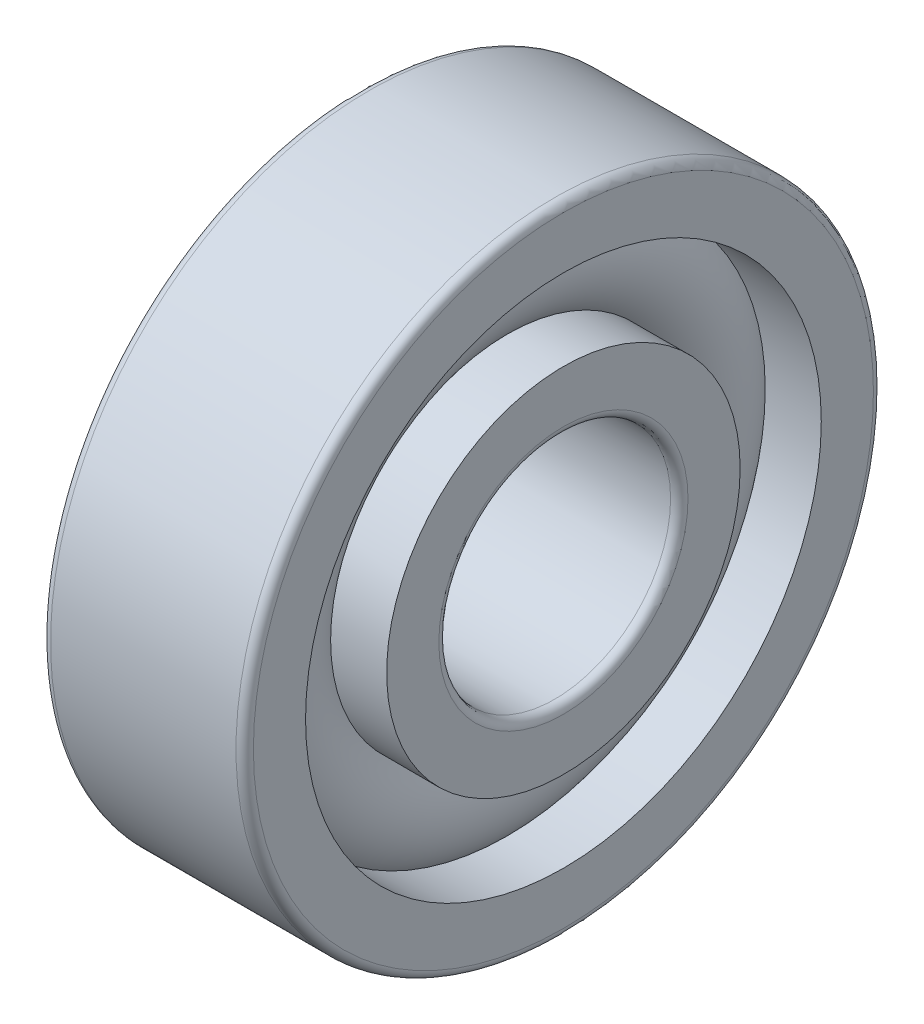
SolidWorks part; units mm, degrees
ref_plane "Plane1" through (0, 0, 0) normal (0, 0, 1) x (1, 0, 0)
ref_plane "Plane2" through (0, 0, 0) normal (0, 1, 0) x (1, 0, 0)
ref_plane "Plane3" through (0, 0, 0) normal (1, 0, 0) x (0, 0, -1)
other "Configuration Table"
sketch "Clipboard" plane through (0, 0, 0) normal (0, 0, 1) x (1, 0, 0)
  line L0 (-10, 0) -> (10, 0) construction
  line L1 (0, 0) -> (22.3471, -0.7804)
  line L2 (0, 0) -> (7.4954, 0.2617)
  line L3 (0, 0) -> (22.3471, -0.7804)
  line L4 (0, 0) -> (-22.3573, -0.3902)
  dimension "BallCLRad" = 7.5
sketch "CagSpiSke" plane through (0, 0, 0) normal (0, 0, 1) x (1, 0, 0)
  line L0 (0.21, 7.15) -> (0.21, 7.85)
  line L1 (0.21, 7.85) -> (-0.21, 7.85)
  line L2 (-0.21, 7.85) -> (-0.21, 7.15)
  line L3 (-0.21, 7.15) -> (0.21, 7.15)
  line L4 (-20.6375, 0) -> (20.6375, 0) construction
  line L5 (0, 0) -> (0, 23.7692) construction
  dimension "OD" = 15.7
  dimension "ID" = 14.3
revolve "CageSpine" add sketch "CagSpiSke" angle 0.001 about L4 reverse direction yes
ref_axis "Axis1" through (-50, 0, 0) along (1, 0, 0)
sketch "CagBalSke" plane through (0, 0, 0) normal (0, 0, 1) x (1, 0, 0)
  line L0 (-2.31, 7.5) -> (2.31, 7.5)
  line L1 (-1.905, 7.5) -> (1.905, 7.5) construction
  line L2 (-10, 0) -> (10, 0) construction
  line L3 (0, 0) -> (0, 24) construction
  arc A0 (2.31, 7.5) -> (-2.31, 7.5) centre (0, 7.5) cw
  dimension "BallCLRad" = 7.5
revolve "CageBall" [suppressed] add sketch "CagBalSke" angle 360 about L1 reverse direction yes
pattern_circular "CageBalls" [suppressed] count 2 every 180 about axis through (-50, 0, 0) along (1, 0, 0)
sketch "CagTrmODSke" plane through (0, 0, 0) normal (0, 0, 1) x (1, 0, 0)
  line L0 (2.311, 7.85) -> (2.311, 9.811)
  line L1 (2.311, 9.811) -> (-2.311, 9.811)
  line L2 (-2.311, 9.811) -> (-2.311, 7.85)
  line L3 (-2.311, 7.85) -> (2.311, 7.85)
  line L4 (-20.6375, 0) -> (20.6375, 0) construction
  line L5 (0, 0) -> (0, 25) construction
  dimension "Width" = 4.622
  dimension "ID" = 15.7
  dimension "OD" = 19.622
revolve "CageTrimOD" [suppressed] cut sketch "CagTrmODSke" angle 360 about L4 reverse direction yes
sketch "CagTrmIDSke" plane through (0, 0, 0) normal (0, 0, 1) x (1, 0, 0)
  line L0 (2.311, 5.191) -> (2.311, 7.15)
  line L1 (2.311, 7.15) -> (-2.311, 7.15)
  line L2 (-2.311, 7.15) -> (-2.311, 5.191)
  line L3 (-2.311, 5.191) -> (2.311, 5.191)
  line L4 (-20.6375, 0) -> (20.6375, 0) construction
  line L5 (0, 0) -> (0, 25) construction
  dimension "Width" = 4.622
  dimension "ID" = 10.382
  dimension "OD" = 14.3
revolve "CageTrimID" [suppressed] cut sketch "CagTrmIDSke" angle 360 about L4 reverse direction yes
sketch "BalSimSke" plane through (0, 0, 0) normal (0, 0, 1) x (1, 0, 0)
  line L0 (-10, 0) -> (10, 0) construction
  line L1 (-10, 7.5) -> (10, 7.5) construction
  line L2 (0, 0) -> (0, 23) construction
  circle A0 centre (0, 7.5) radius 2.1
  dimension "BallCLRad" = 7.5
  dimension "Ball_diameter" = 4.2
revolve "BallsSimplified" add sketch "BalSimSke" angle 360 about L0
sketch "BalDetSke" plane through (0, 0, 0) normal (0, 0, 1) x (1, 0, 0)
  line L0 (-2.1, 7.5) -> (2.1, 7.5)
  line L1 (-1.905, 7.5) -> (1.905, 7.5) construction
  line L2 (0, 0) -> (0, 25) construction
  arc A0 (2.1, 7.5) -> (-2.1, 7.5) centre (0, 7.5) cw
  dimension "BallCLRad" = 7.5
  dimension "Ball_diameter" = 4.2
revolve "BallDetailed" [suppressed] add sketch "BalDetSke" angle 360 about L1 reverse direction yes
sketch "InnRacSke" plane through (0, 0, 0) normal (0, 0, 1) x (1, 0, 0)
  line L0 (-1.5315, 6.1) -> (-3.5, 6.1)
  line L1 (-3.5, 6.1) -> (-3.5, 4.3)
  line L2 (-3.2, 4) -> (3.2, 4)
  line L3 (3.5, 4.3) -> (3.5, 6.1)
  line L4 (3.5, 6.1) -> (1.5315, 6.1)
  line L5 (-20.6375, 0) -> (20.6375, 0) construction
  line L6 (0, 0) -> (0, 30) construction
  arc A0 (-3.5, 4.3) -> (-3.2, 4) centre (-3.2, 4.3) ccw
  arc A1 (3.2, 4) -> (3.5, 4.3) centre (3.2, 4.3) ccw
  arc A2 (1.5315, 6.1) -> (-1.5315, 6.1) centre (0, 7.5) cw
  dimension "BallCLRad" = 7.5
  dimension "Fillet_radius" = 0.3
  dimension "Ball_diameter" = 4.15
  dimension "ID" = 8
  dimension "OD" = 12.2
  dimension "Width" = 7
revolve "InnerRace" add sketch "InnRacSke" angle 360 about L5 reverse direction yes
sketch "OutRacSke" plane through (0, 0, 0) normal (0, 0, 1) x (1, 0, 0)
  line L0 (-1.5315, 8.9) -> (-3.5, 8.9)
  line L1 (-3.5, 8.9) -> (-3.5, 10.7)
  line L2 (-3.2, 11) -> (3.2, 11)
  line L3 (3.5, 10.7) -> (3.5, 8.9)
  line L4 (3.5, 8.9) -> (1.5315, 8.9)
  line L5 (-20.6375, 0) -> (20.6375, 0) construction
  line L6 (0, 0) -> (0, 30) construction
  arc A0 (-3.5, 10.7) -> (-3.2, 11) centre (-3.2, 10.7) cw
  arc A1 (3.2, 11) -> (3.5, 10.7) centre (3.2, 10.7) cw
  arc A2 (1.5315, 8.9) -> (-1.5315, 8.9) centre (0, 7.5) ccw
  dimension "BallCLRad" = 7.5
  dimension "Fillet_radius" = 0.3
  dimension "Ball_diameter" = 4.15
  dimension "Width" = 7
revolve "OuterRace" add sketch "OutRacSke" angle 360 about L5 reverse direction yes
pattern_circular "BallsDetailed" [suppressed] count 2 every 180 about axis through (-50, 0, 0) along (1, 0, 0)
equation "\"BallCLRad@Clipboard\" = ( \"OD@OutRacSke\" + \"ID@InnRacSke\" ) / 4"
equation "\"BallCLRad@BalSimSke\" = \"BallCLRad@Clipboard\""
equation "\"BallCLRad@BalDetSke\" = \"BallCLRad@Clipboard\""
equation "\"BallCLRad@InnRacSke\" = \"BallCLRad@Clipboard\""
equation "\"BallCLRad@OutRacSke\" = \"BallCLRad@Clipboard\""
equation "\"Ball_diameter@InnRacSke\" = \"Ball_diameter@BalDetSke\" - 0.05"
equation "\"Ball_diameter@OutRacSke\" = \"Ball_diameter@BalDetSke\" - 0.05"
equation "\"Ball_diameter@BalSimSke\" = \"Ball_diameter@BalDetSke\""
equation "\"Width@OutRacSke\" = \"Width@InnRacSke\""
equation "\"Fillet_radius@OutRacSke\" = \"Fillet_radius@InnRacSke\""
equation "\"Max_count@Clipboard\" = int( 3.14159265 / atn(( \"Ball_diameter@BalDetSke\" / 2) / sqr( \"BallCLRad@Clipboard\"  *  \"BallCLRad@Clipboard\" - ( \"Ball_diameter@BalDetSke\" / 2) *  ( \"Ball_diameter@BalDetSke\" / 2))))"
equation "\"Max_count@Clipboard\" = ((sgn( \"Max_count@Clipboard\" - \"Count@Clipboard\" )-1)*( \"Max_count@Clipboard\" - \"Count@Clipboard\" ))/-2+ \"Count@Clipboard\""
equation "\"Count@BallsDetailed\" = int( \"Show_count@Clipboard\" ) "
equation "\"Count@BallsDetailed\" = ((sgn( \"Count@BallsDetailed\" - \"Max_count@Clipboard\" )-1)*( \"Count@BallsDetailed\" - \"Max_count@Clipboard\" ))/-2+ \"Max_count@Clipboard\""
equation "\"Count@BallsDetailed\" = ((sgn( \"Count@BallsDetailed\" - \"Min_count@Clipboard\" )+1)*( \"Count@BallsDetailed\" - \"Min_count@Clipboard\"))/2 +\"Min_count@Clipboard\""
equation "\"Angle@BallsDetailed\" = 360.0 / \"Max_count@Clipboard\""
equation "\"BallCLRad@CagBalSke\" = \"BallCLRad@Clipboard\""
equation "\"Count@CageBalls\" = \"Count@BallsDetailed\""
equation "\"Angle@CageBalls\" = \"Angle@BallsDetailed\""
equation "\"Angle@CageSpine\" =  \"Angle@CageBalls\" * ( \"Count@CageBalls\" -1 + int( \"Count@CageBalls\" / \"Max_count@Clipboard\" ) )  + 0.001 -  int( \"Count@CageBalls\" / \"Max_count@Clipboard\" ) * 0.001"
equation "\"Angle@CageSpine\" =  \"Angle@CageSpine\" * int( \"Min_count@Clipboard\" / 2) + int(1 / \"Min_count@Clipboard\")  * 0.001"
equation "\"CageWallOD@CagBalSke\" =  \"Ball_diameter@BalDetSke\" * 1.1"
equation "\"Thickness@CagSpiSke\" =  \"Ball_diameter@BalDetSke\" * 0.1"
equation "\"OD@CagTrmODSke\" = \"BallCLRad@Clipboard\" * 2 + \"CageWallOD@CagBalSke\" + 0.002"
equation "\"ID@CagTrmODSke\" = \"BallCLRad@Clipboard\" * 2 + \"Ball_diameter@BalDetSke\" / 6"
equation "\"OD@CagTrmIDSke\" = \"BallCLRad@Clipboard\" * 2 - \"Ball_diameter@BalDetSke\" / 6"
equation "\"ID@CagTrmIDSke\" = \"BallCLRad@Clipboard\" * 2 - \"CageWallOD@CagBalSke\" + 0.002"
equation "\"OD@CagSpiSke\" = \"ID@CagTrmODSke\""
equation "\"ID@CagSpiSke\" = \"OD@CagTrmIDSke\""
equation "\"Width@CagTrmODSke\" = \"CageWallOD@CagBalSke\" + 0.002"
equation "\"Width@CagTrmIDSke\" = \"CageWallOD@CagBalSke\" + 0.002"
